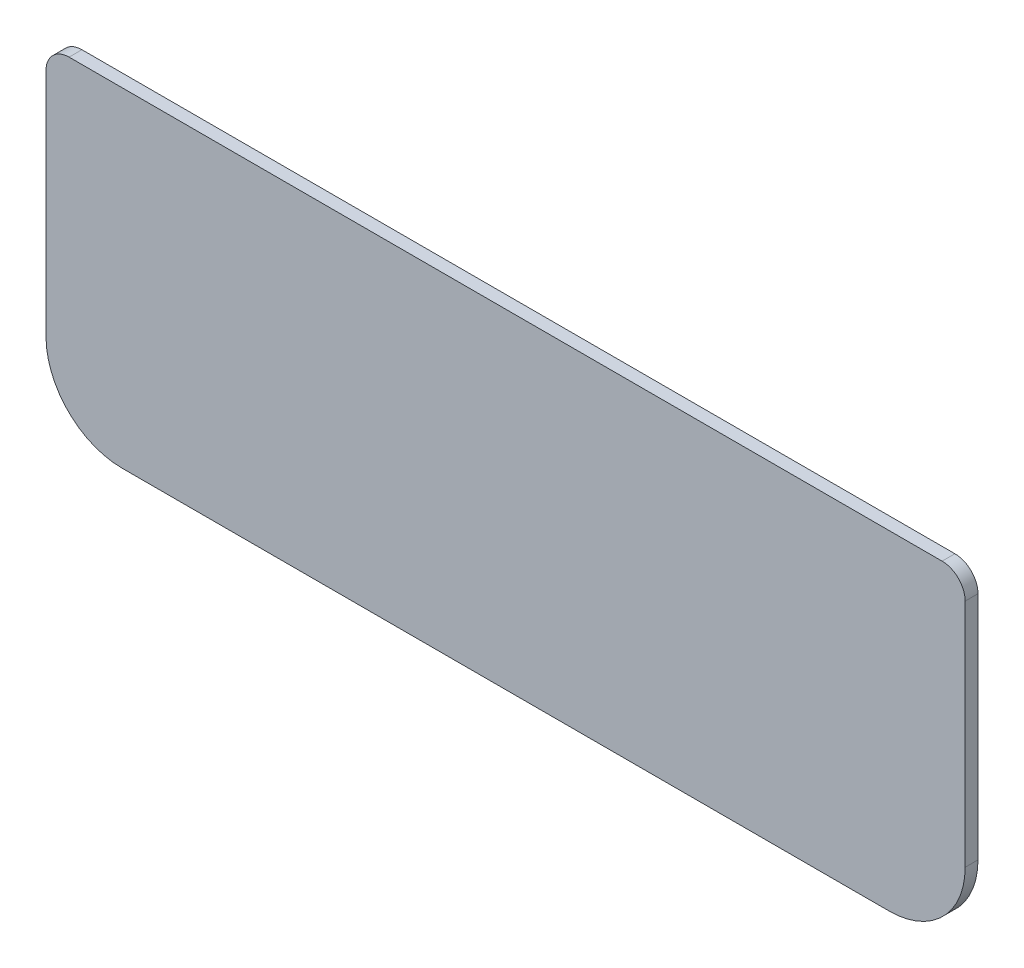
SolidWorks part; units mm, degrees
ref_plane "Plan de face" through (0, 0, 0) normal (0, 0, 1) x (1, 0, 0)
ref_plane "Plan de dessus" through (0, 0, 0) normal (0, 1, 0) x (1, 0, 0)
ref_plane "Plan de droite" through (0, 0, 0) normal (1, 0, 0) x (0, 0, -1)
sketch "Esquisse20" plane through (0, 0, 0) normal (0, 0, 1) x (1, 0, 0)
  line L1 (14.8, -2) -> (164.37, -2)
  line L2 (0, 12.8) -> (0, 57.73)
  line L3 (4.5, 62.23) -> (174.67, 62.23)
  line L4 (179.17, 12.8) -> (179.17, 57.73)
  arc A0 (0, 57.73) -> (4.5, 62.23) centre (4.5, 57.73) cw
  arc A1 (174.67, 62.23) -> (179.17, 57.73) centre (174.67, 57.73) cw
  arc A2 (164.37, -2) -> (179.17, 12.8) centre (164.37, 12.8) ccw
  arc A3 (14.8, -2) -> (0, 12.8) centre (14.8, 12.8) cw
  point P7 (0, 62.23)
  point P10 (179.17, 62.23)
  point P14 (179.17, -2)
  point P17 (0, -2)
extrude "Boss.-Extru.1" add sketch "Esquisse20" along normal blind 2.5
